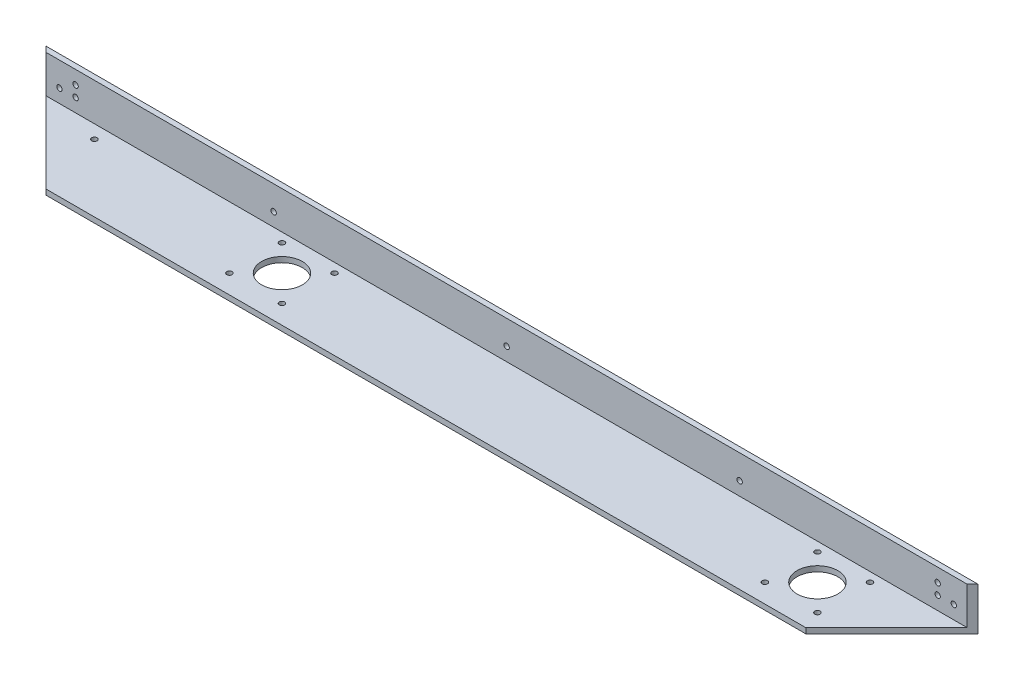
SolidWorks part; units mm, degrees
ref_plane "Front Plane" through (0, 0, 0) normal (0, 0, 1) x (1, 0, 0)
ref_plane "Top Plane" through (0, 0, 0) normal (0, 1, 0) x (1, 0, 0)
ref_plane "Right Plane" through (0, 0, 0) normal (1, 0, 0) x (0, 0, -1)
sketch "Sketch1" plane through (0, 0, 0) normal (1, 0, 0) x (0, 0, -1)
  line L0 (0, 0) -> (-50.8, 0)
  line L1 (-50.8, 0) -> (-50.8, 3.175)
  line L2 (-50.8, 3.175) -> (-3.175, 3.175)
  line L3 (-3.175, 3.175) -> (-3.175, 25.4)
  line L4 (-3.175, 25.4) -> (0, 25.4)
  line L5 (0, 25.4) -> (0, 0)
  dimension "LHeight" = 25.4
  dimension "LWidth" = 50.8
  dimension "LMaterialThickness" = 3.175
  dimension "D1" = 47.625
  dimension "D2" = 22.225
  dimension "D3" = 3.175
extrude "Boss-Extrude1" add sketch "Sketch1" along normal blind 550
chamfer "Chamfer7" distance 50.8 angle 45 1 edges at (0, 1.5875, 50.8)
chamfer "Chamfer8" distance 50.8 angle 45 1 edges at (550, 1.5875, 50.8)
sketch "BotthomHoles-Sketch2" plane through (0, 3.175, 0) normal (0, 1, 0) x (1, 0, 0)
  line L0 (546.825, -3.175) -> (3.175, -3.175) construction
  line L1 (550, 0) -> (0, 0) construction
  circle A0 centre (479.425, -24.175) radius 12
  circle A2 centre (463.925, -8.675) radius 1.5875
  circle A3 centre (494.925, -8.675) radius 1.5875
  circle A6 centre (463.925, -39.675) radius 1.5875
  circle A7 centre (494.925, -39.675) radius 1.5875
  circle A8 centre (39.6875, -11.1125) radius 1.5875
  circle A10 centre (178.925, -39.675) radius 1.5875
  circle A11 centre (147.925, -39.675) radius 1.5875
  circle A12 centre (178.925, -8.675) radius 1.5875
  circle A13 centre (147.925, -8.675) radius 1.5875
  circle A14 centre (163.425, -24.175) radius 12
  dimension "D9" = 3.175
  dimension "D10" = 24
  dimension "D13" = 3.175
  dimension "D2" = 8.675
  dimension "D5" = 15.5
  dimension "D6" = 31
  dimension "D7" = 15.5
  dimension "D8" = 31
  dimension "D11" = 21
  dimension "D3" = 70.575
  dimension "D4" = 11.1125
  dimension "D12" = 39.6875
  dimension "D15" = 31
  dimension "D16" = 15.5
  dimension "D17" = 316
extrude "BottomHoles-Cut-Extrude1" cut sketch "BotthomHoles-Sketch2" against normal through all
sketch "RightSideHoles-Sketch3" plane through (0, 0, 0) normal (0, 0, -1) x (-1, 0, 0)
  line L0 (-550, 0) -> (-550, 25.4) construction
  line L1 (0, 0) -> (0, 25.4) construction
  line L2 (-550, 25.4) -> (0, 25.4) construction
  circle A1 centre (-529.3625, 17.4625) radius 1.5875
  circle A2 centre (-538.8875, 11.1125) radius 1.5875
  circle A3 centre (-529.3625, 11.1125) radius 1.5875
  circle A4 centre (-11.1125, 11.1125) radius 1.5875
  circle A5 centre (-20.6375, 11.1125) radius 1.5875
  circle A6 centre (-20.6375, 17.4625) radius 1.5875
  circle A8 centre (-412.5, 11.1125) radius 1.5875
  circle A9 centre (-275, 11.1125) radius 1.5875
  circle A10 centre (-137.5, 11.1125) radius 1.5875
  dimension "D4" = 11.1125
  dimension "D7" = 3.175
  dimension "D2" = 20.6375
  dimension "D6" = 20.6375
  dimension "D8" = 137.5
  dimension "D9" = 137.5
  dimension "D10" = 137.5
  dimension "D5" = 11.1125
  dimension "D11" = 11.1125
  dimension "D3" = 7.9375
extrude "RightSideHoles-Cut-Extrude2" cut sketch "RightSideHoles-Sketch3" against normal through all
equation "\"LowerRailWidth\"= 2.00in"
equation "\"LowerRailHeight\"= 1.00in"
equation "\"RailThickness\"= .125in'Spec"
equation "\"SideRailHoleY1FromEdge\"= \"HoleOffsetFromEdge\""
equation "\"SideRailHoleX1FromSide\"= \"HoleOffsetFromSide\""
equation "\"StepperHoleDiameter\"= 24mm"
equation "\"StepperMountingHoleDiameter\"= 3.175mm"
equation "\"SideRailLength\"= 550mm"
equation "\"StepperMountingHoleDistance\"= 31mm'Spec"
equation "\"VSWidth\"= 1.25in'Spec"
equation "\"StepperMountingHoleOffsetFromLeftOrRightSide\"= \"StepperMountingHoleOffsetFromItsSide\" + \"RailThickness\""
equation "\"HoleOffsetFromEdge\"= \"RailThickness\" * 2.5"
equation "\"HoleOffsetFromSide\"= \"RailThickness\" * 3.5"
equation "\"StepperMountingHoleOffsetFromItsSide\"= 5.5mm'Spec"
equation "\"SideRailHoleX2FromSide\"= \"VSWidth\" - \"HoleOffsetFromEdge\" - \"RailThickness\"'Equals 20.6375"
equation "\"FasteningHoleDiameter\"= .125in"
equation "\"SideRailHoleY2FromSide\"= \"HoleOffsetFromSide\""
equation "\"LHeight@Sketch1\"=\"LowerRailHeight\""
equation "\"LWidth@Sketch1\"=\"LowerRailWidth\""
equation "\"D1@Chamfer7\"=\"LowerRailWidth\""
equation "\"D1@Chamfer8\"=\"LowerRailWidth\""
equation "\"D2@BotthomHoles-Sketch2\" = \"StepperMountingHoleOffsetFromLeftOrRightSide\""
equation "\"D5@BotthomHoles-Sketch2\" = \"StepperMountingHoleDistance\" / 2"
equation "\"D6@BotthomHoles-Sketch2\" = \"StepperMountingHoleDistance\""
equation "\"D7@BotthomHoles-Sketch2\" = \"StepperMountingHoleDistance\" / 2"
equation "\"D8@BotthomHoles-Sketch2\" = \"StepperMountingHoleDistance\""
equation "\"D9@BotthomHoles-Sketch2\" = \"StepperMountingHoleDiameter\""
equation "\"D10@BotthomHoles-Sketch2\" = \"StepperHoleDiameter\""
equation "\"D2@RightSideHoles-Sketch3\" = \"SideRailHoleX2FromSide\""
equation "\"D4@RightSideHoles-Sketch3\" = \"SideRailHoleY2FromSide\""
equation "\"D7@RightSideHoles-Sketch3\" = \"FasteningHoleDiameter\""
equation "\"D1@Boss-Extrude1\"=\"SideRailLength\""
equation "\"D6@RightSideHoles-Sketch3\"=\"SideRailHoleX2FromSide\""
equation "\"BedOverlap\"= 20mm"
equation "\"BedThirdSize\"= 70mm"
equation "\"BedInnerSquareWidth\"= \"BedThirdSize\" * 3'Equals 210"
equation "\"BedInnerSquareLength\"= \"BedInnerSquareWidth\""
equation "\"BedLWidth\"= \"BedThirdSize\" + \"BedOverlap\"'Equals 90"
equation "\"BedLength\"= \"BedInnerSquareLength\" + \"BedLWidth\" * 2 - \"BedOverlap\" * 2 + \"BedIncreasedByLength\"'Equals 350"
equation "\"DistanceBetweenFrontToBackStepperHoles\"= \"BedLength\" - \"DistanceFromBedFrontToFirstLeftStepperHole\"'Equals 316"
equation "\"D3@BotthomHoles-Sketch2\"=\"DistanceFromFrontSideToFirstLeftStepperHole\""
equation "\"DistanceFromBedFrontToFirstLeftStepperHole\"= \"LeadScrewNutPadSize\" + 10mm'Equals 34"
equation "\"DistanceFromFrontSideToBedFront\"= \"RailThickness\" + \"BeltTensionerDepth\" + 10mm'Equals 36.575"
equation "\"20TGT2PulleyDiameter\"= 17.9mm'Spec"
equation "\"BeltTensionerBackWallThickness\"= 4mm"
equation "\"BeltTensionerSpaceBetweenPulleyAndWall\"= 1.5mm"
equation "\"BeltTensionerInnerDepth\"= \"20TGT2PulleyDiameter\" + \"BeltTensionerSpaceBetweenPulleyAndWall\""
equation "\"BeltTensionerDepth\"= \"BeltTensionerBackWallThickness\" + \"BeltTensionerInnerDepth\"'Equals 23.4"
equation "\"BedIncreasedByLength\"= 0mm"
equation "\"LowerCornerBlockWidth\"= \"LowerRailWidth\" - \"RailThickness\" * 2'Room for left front stepper"
equation "\"D4@BotthomHoles-Sketch2\"=\"LowerCornerBlockY1FromSide\""
equation "\"D12@BotthomHoles-Sketch2\"=\"CornerEnclosureOffset\""
equation "\"D13@BotthomHoles-Sketch2\"=\"FasteningHoleDiameter\""
equation "\"CornerEnclosureOffset\"= \"LowerCornerBlockWidth\" - \"HoleOffsetFromEdge\" + \"RailThickness\""
equation "\"LowerCornerBlockY1FromSide\"= \"HoleOffsetFromSide\""
equation "\"D15@BotthomHoles-Sketch2\"=\"StepperMountingHoleDistance\""
equation "\"D16@BotthomHoles-Sketch2\"=\"StepperMountingHoleDistance\"/2"
equation "\"D17@BotthomHoles-Sketch2\"=\"DistanceBetweenFrontToBackStepperHoles\""
equation "\"DistanceFromFrontSideToFirstLeftStepperHole\"= \"DistanceFromFrontSideToBedFront\" + \"DistanceFromBedFrontToFirstLeftStepperHole\"'Equals 70.575"
equation "\"LeadScrewNutMountingHoleFlangeDiameter\"= 22mm'Spec"
equation "\"LeadScrewNutPadSize\"= \"LeadScrewNutMountingHoleFlangeDiameter\" + 2mm'Equals 24"
equation "\"LeftOrRightEnclosureOffsets\"= \"SideRailLength\" / 4"
equation "\"D8@RightSideHoles-Sketch3\"=\"LeftOrRightEnclosureOffsets\""
equation "\"D9@RightSideHoles-Sketch3\"=\"LeftOrRightEnclosureOffsets\""
equation "\"D10@RightSideHoles-Sketch3\"=\"LeftOrRightEnclosureOffsets\""
equation "\"D5@RightSideHoles-Sketch3\"=\"SideRailHoleX1FromSide\""
equation "\"D11@RightSideHoles-Sketch3\"=\"SideRailHoleX1FromSide\""
equation "\"D3@RightSideHoles-Sketch3\"=\"SideRailHoleY1FromEdge\""
